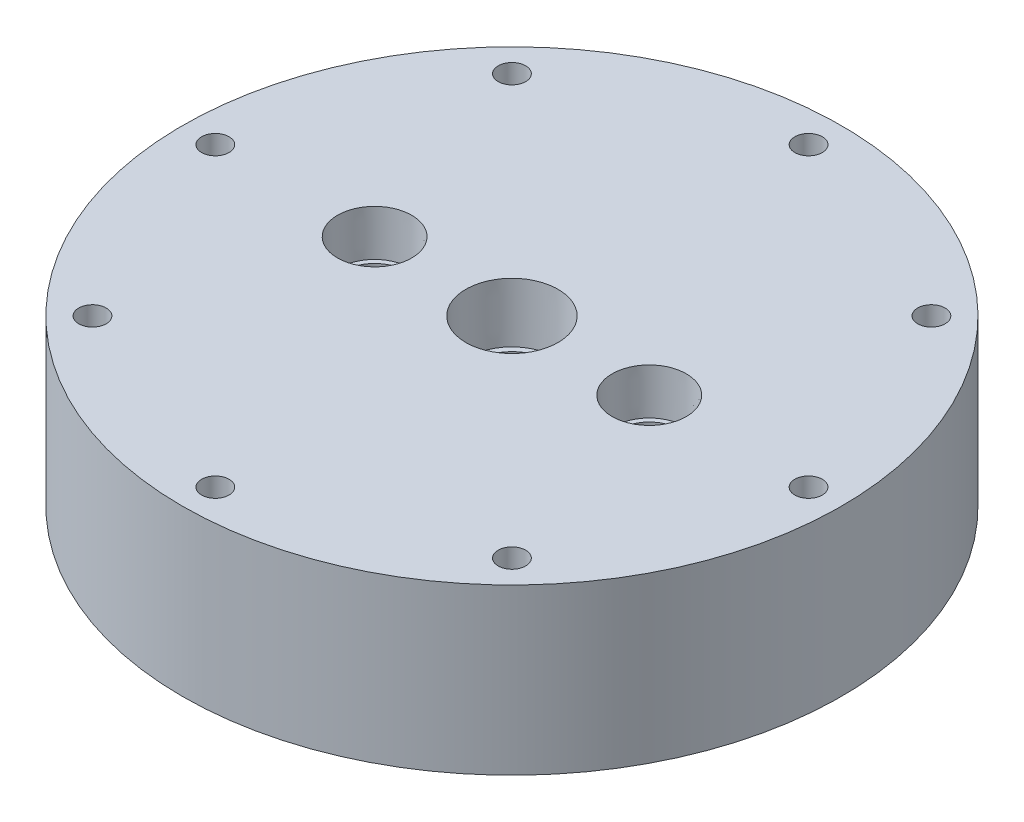
SolidWorks part; units mm, degrees
ref_plane "Front Plane" through (0, 0, 0) normal (0, 0, 1) x (1, 0, 0)
ref_plane "Top Plane" through (0, 0, 0) normal (0, 1, 0) x (1, 0, 0)
ref_plane "Right Plane" through (0, 0, 0) normal (1, 0, 0) x (0, 0, -1)
ref_axis "Axial" through (0, 53.34, 0) along (0, -1, 0)
ref_plane "Bottom Plane" through (0, -50.8, 0) normal (0, 1, 0) x (1, 0, 0)
sketch "Sketch1" plane through (0, 0, 0) normal (0, 1, 0) x (1, 0, 0)
  circle A0 centre (0, 0) radius 76.2
  dimension "D1" = 152.4
extrude "Billet" add sketch "Sketch1" against normal blind 50.8
sketch "Sketch3" plane through (0, -50.8, 0) normal (0, 1, 0) x (1, 0, 0)
  line L0 (0, 81.5114) -> (0, -83.2162) construction
  circle A0 centre (0, 0) radius 19.05
  dimension "D1" = 38.1
  dimension "D2" = 0
extrude "Lox Plate" cut sketch "Sketch3" along normal blind 13.97
sketch "Sketch5" plane through (0, -50.8, 0) normal (0, 1, 0) x (1, 0, 0)
  line L0 (0, 57.2178) -> (0, -49.9723) construction
  circle A0 centre (0, 0) radius 13.97
  dimension "D1" = 27.94
  dimension "D2" = 0
extrude "Lox Dome" cut sketch "Sketch5" along normal blind 20.32
sketch "Sketch7" plane through (0, 0, 0) normal (0, 1, 0) x (1, 0, 0)
  circle A1 centre (0, 0) radius 76.2
  dimension "D2" = 152.4
extrude "Top Mill" cut sketch "Sketch7" against normal blind 12.7
sketch "Sketch11" plane through (0, -50.8, 0) normal (0, 1, 0) x (1, 0, 0)
  line L0 (0, 82.3071) -> (0, -82.946) construction
  circle A0 centre (0, 68.58) radius 3.175
  dimension "D1" = 6.35
  dimension "D2" = 68.58
extrude "1/4\" Bolt Hole" cut sketch "Sketch11" along normal up to next
pattern_circular "Bolt Pattern" count 8 over 360 about axis through (0, 53.34, 0) along (0, -1, 0) of "1/4\" Bolt Hole"
sketch "Sketch12" plane through (0, -50.8, 0) normal (0, 1, 0) x (1, 0, 0)
  circle A0 centre (0, 0) radius 60.96
  dimension "D1" = 121.92
extrude "Kerosene Plate" cut sketch "Sketch12" along normal blind 10.16
hole_wizard "Lox Inlet-1/2 NPT Tapped Hole3" positions "Sketch20" profile "Sketch21" size "1/2" standard "ANSI Inch" end condition through all
sketch "Sketch20" plane through (0, -12.7, 0) normal (0, 1, 0) x (1, 0, 0)
  line L0 (0, 40.1697) -> (0, -38.6779) construction
  point P8 (0, 0)
  dimension "D1" = 0
sketch "Sketch21" plane through (0, -12.7, 0) normal (1, 0, 0) x (0, 0, 1)
  line L0 (0, 0) -> (0, 38.1)
  line L1 (0, 38.1) -> (8.9281, 38.1)
  line L2 (-10.2617, 13.462) -> (-10.6647, 0) construction
  line L3 (8.9281, 38.1) -> (8.9281, 13.462)
  line L4 (8.9281, 13.462) -> (10.2617, 13.462)
  line L5 (10.2617, 13.462) -> (10.6647, 0)
  line L7 (10.6647, 0) -> (0, 0)
  line L8 (0, -6.35) -> (0, 107.95) construction
  line L11 (-8.9281, 13.462) -> (-10.2617, 13.462) construction
  dimension "Thru Tap Drill Dia." = 17.8562
  dimension "Thru Tap Drill Depth" = 38.1
  dimension "Thread Dia." = 21.3295
  dimension "Thread Angle" = 3.43
  dimension "Thread Depth" = 13.462
sketch "Sketch26" plane through (0, -36.83, 0) normal (0, -1, 0) x (1, 0, 0)
  line L0 (0, 56.6416) -> (0, -116.1839) construction
  circle A0 centre (0, 0) radius 16.51
  circle A1 centre (0, 0) radius 17.78
  dimension "D1" = 35.56
  dimension "D2" = 33.02
  dimension "D3" = 0
extrude "Lox Plate O Ring" cut sketch "Sketch26" against normal blind 1.27
hole_wizard "Kerosene Inlet-3/8 NPT Tapped Hole1" positions "Sketch24" profile "Sketch25" size "3/8" standard "ANSI Inch" end condition through all
sketch "Sketch24" plane through (0, -12.7, 0) normal (0, 1, 0) x (1, 0, 0)
  point P0 (-31.75, 0)
  point P2 (31.75, 0)
  dimension "D1" = 31.75
  dimension "D2" = 31.75
sketch "Sketch25" plane through (-31.75, -12.7, 0) normal (1, 0, 0) x (0, 0, 1)
  line L0 (0, 0) -> (0, 38.1)
  line L1 (0, 38.1) -> (7.1374, 38.1)
  line L2 (-8.2632, 10.414) -> (-8.575, 0) construction
  line L3 (7.1374, 38.1) -> (7.1374, 10.414)
  line L4 (7.1374, 10.414) -> (8.2632, 10.414)
  line L5 (8.2632, 10.414) -> (8.575, 0)
  line L7 (8.575, 0) -> (0, 0)
  line L8 (0, -6.35) -> (0, 107.95) construction
  line L11 (-7.1374, 10.414) -> (-8.2632, 10.414) construction
  dimension "Thru Tap Drill Dia." = 14.2748
  dimension "Thru Tap Drill Depth" = 38.1
  dimension "Thread Dia." = 17.15
  dimension "Thread Angle" = 3.43
  dimension "Thread Depth" = 10.414
